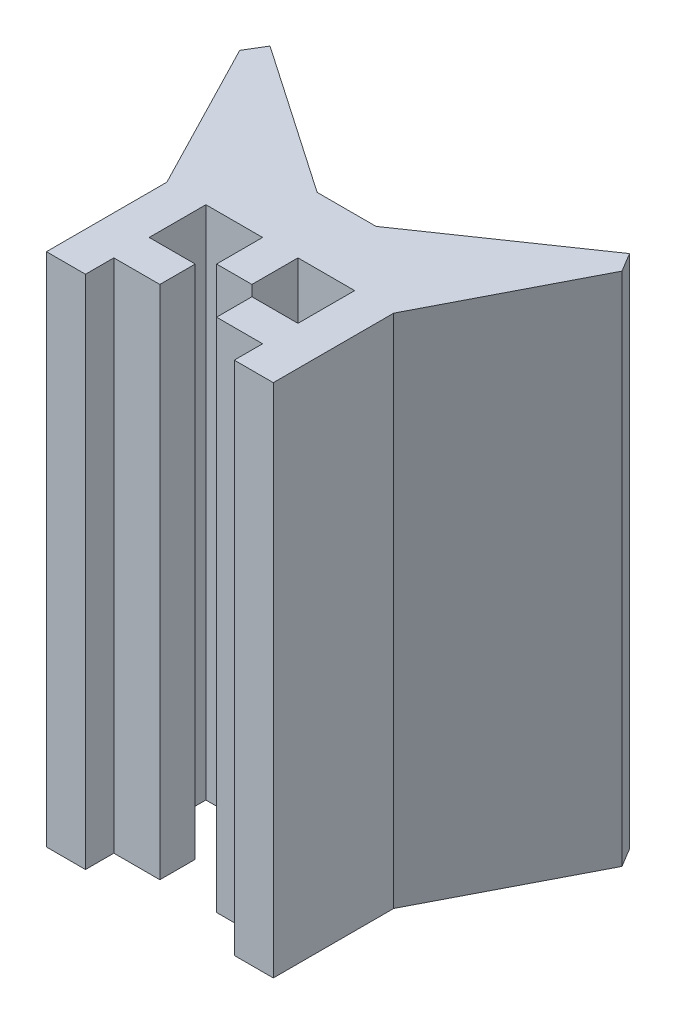
SolidWorks part; units mm, degrees
ref_plane "Plan de face" through (0, 0, 0) normal (0, 0, 1) x (1, 0, 0)
ref_plane "Plan de dessus" through (0, 0, 0) normal (0, 1, 0) x (1, 0, 0)
ref_plane "Plan de droite" through (0, 0, 0) normal (1, 0, 0) x (0, 0, -1)
sketch "Base" plane through (0, 0, 0) normal (0, 1, 0) x (1, 0, 0)
  line L0 (-3.85, -2.4) -> (-3.85, 2.4)
  line L1 (-3.85, 2.4) -> (-10.1, 2.4)
  line L2 (-10.1, 2.4) -> (-10.1, 10.1)
  line L3 (-10.1, 10.1) -> (-2.4, 10.1)
  line L4 (-2.4, 10.1) -> (-2.4, 3.85)
  line L5 (-2.4, 3.85) -> (2.4, 3.85)
  line L6 (0, -24.6801) -> (0, 24.6801) construction
  line L7 (2.4, 10.1) -> (2.4, 3.85)
  line L8 (10.1, 10.1) -> (2.4, 10.1)
  line L9 (10.1, 2.4) -> (10.1, 10.1)
  line L10 (3.85, 2.4) -> (10.1, 2.4)
  line L11 (3.85, -2.4) -> (3.85, 2.4)
  line L12 (-28.5456, 0) -> (28.5456, 0) construction
  line L13 (3.85, -2.4) -> (10.1, -2.4)
  line L14 (10.1, -2.4) -> (10.1, -6.2477)
  line L20 (-10.1, -2.4) -> (-10.1, -6.2477)
  line L21 (-3.85, -2.4) -> (-10.1, -2.4)
  line L24 (-15.4, 10.1023) -> (-15.4, -6.2477)
  line L26 (15.4, 10.1023) -> (15.4, -6.2477)
  line L29 (-10.1, -6.2477) -> (-15.4, -6.2477)
  line L30 (10.1, -6.2477) -> (15.4, -6.2477)
  line L32 (-25.9505, 30.5397) -> (-15.4, 10.1023)
  line L33 (0, 0) -> (0, 38.6251) construction
  line L34 (24.4075, 33.1124) -> (4, 19.1023)
  line L35 (4, 19.1023) -> (-4, 19.1023)
  line L36 (-24.4075, 33.1124) -> (-4, 19.1023)
  line L38 (25.9505, 30.5397) -> (15.4, 10.1023)
  line L42 (24.4075, 33.1124) -> (25.9505, 30.5397)
  line L43 (-24.4075, 33.1124) -> (-25.9505, 30.5397)
  point P2 (-3.85, 0)
  point P3 (0, 3.85)
  point P27 (0, 0)
  point P29 (0, 0)
  point P30 (0, 0)
  point P31 (0, 0)
  point P38 (0, 19.1023)
  dimension "D6" = 24.7538
  dimension "D1" = 4.8
  dimension "D2" = 4.8
  dimension "D3" = 6.25
  dimension "D4" = 7.7
  dimension "D5" = 23
  dimension "D7" = 9
  dimension "D9" = 16.35
  dimension "D10" = 8
  dimension "D11" = 3
  dimension "D12" = 5.3
extrude "Boss.-Extru.2" add sketch "Base" along normal blind 70 contours L34 L35 L36 L43 L32 L24 L29 L20 L21 L0 L1 L2 L3 L4 L5 L7 L8 L9 L10 L11 L13 L14 L30 L26 L38 L42
